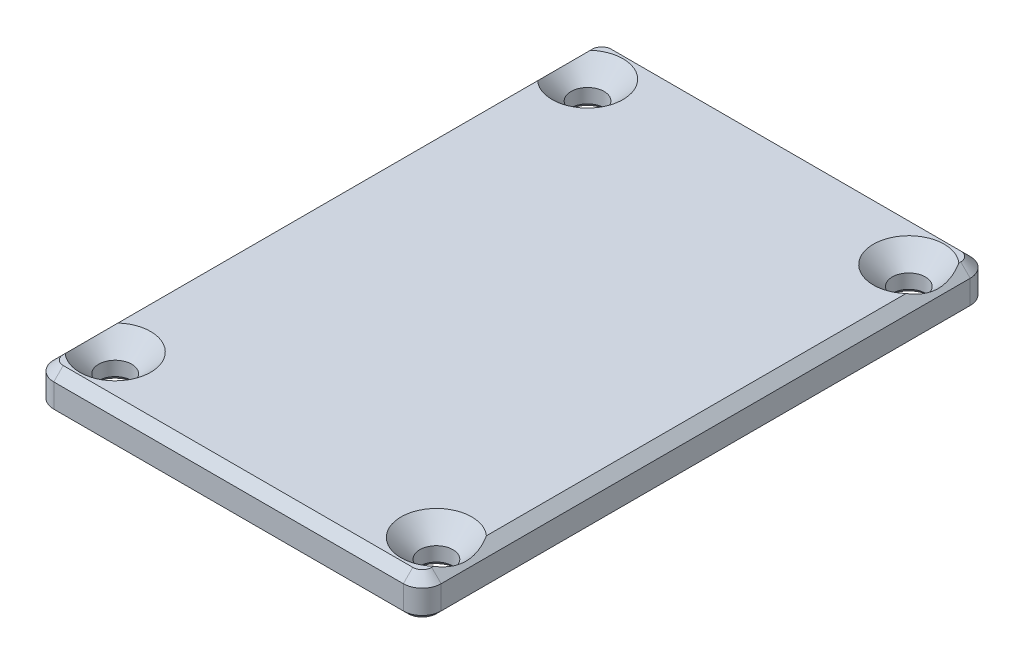
SolidWorks part; units mm, degrees
ref_plane "Спереди" through (0, 0, 0) normal (0, 0, 1) x (1, 0, 0)
ref_plane "Сверху" through (0, 0, 0) normal (0, 1, 0) x (1, 0, 0)
ref_plane "Справа" through (0, 0, 0) normal (1, 0, 0) x (0, 0, -1)
sketch "Эскиз1" plane through (0, 0, 0) normal (0, 1, 0) x (1, 0, 0)
  line L1 (-20.5, -30) -> (20.5, -30)
  line L2 (-20.5, -30) -> (-20.5, 30)
  line L3 (-20.5, 30) -> (20.5, 30)
  line L4 (20.5, -30) -> (20.5, 30)
  line L5 (0, 30) -> (0, -30) construction
  line L6 (-20.5, 0) -> (20.5, 0) construction
  point P0 (0, 0)
  dimension "D1" = 60
  dimension "D2" = 41
extrude "Бобышка-Вытянуть1" add sketch "Эскиз1" along normal blind 4
sketch "Эскиз2" plane through (0, 4, 0) normal (0, 1, 0) x (1, 0, 0)
  line L0 (0, 32.2776) -> (0, 0) construction
  line L1 (0, 0) -> (26.8846, 0) construction
  line L2 (20.5, -30) -> (20.5, 30) construction
  circle A0 centre (17, 25) radius 1.75
  circle A1 centre (17, -25) radius 1.75
  circle A2 centre (-17, -25) radius 1.75
  circle A3 centre (-17, 25) radius 1.75
  dimension "D1" = 25
  dimension "D2" = 3.5
  dimension "D3" = 3.5
extrude "Вырез-Вытянуть1" cut sketch "Эскиз2" against normal through all
fillet "Скругление1" radius 2 4 edges at (20.5, 2, -30) (-20.5, 2, -30) (-20.5, 2, 30) (20.5, 2, 30)
chamfer "Фаска2" distance 1 angle 45 8 edges at (-20.5, 4, 0) (19.9142, 4, -29.4142) (-19.9142, 4, -29.4142) (0, 4, -30) (-19.9142, 4, 29.4142) (0, 4, 30) (19.9142, 4, 29.4142) (20.5, 4, 0)
chamfer "Фаска1" distance 2 angle 45 4 edges at (-17, 4, 26.75) (17, 4, 23.25) (-17, 4, -26.75) (17, 4, -23.25)
chamfer "Фаска3" distance 0.5 angle 45 12 edges at (-19.9142, 0, -29.4142) (-20.5, 0, 0) (-19.9142, 0, 29.4142) (0, 0, 30) (19.9142, 0, 29.4142) (20.5, 0, 0) (19.9142, 0, -29.4142) (0, 0, -30) (17, 0, -23.25) (17, 0, 23.25) (-17, 0, 26.75) (-17, 0, -26.75)
